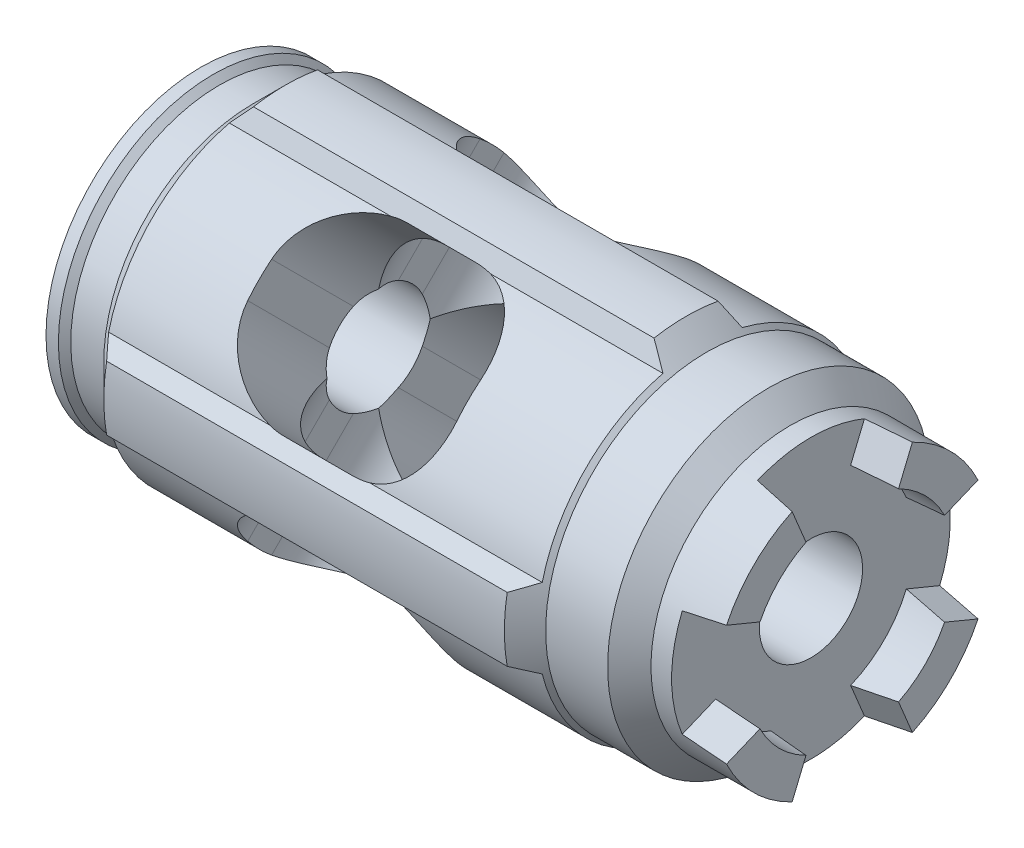
SolidWorks part; units mm, degrees
ref_plane "Front Plane" through (0, 0, 0) normal (0, 0, 1) x (1, 0, 0)
ref_plane "Top Plane" through (0, 0, 0) normal (0, 1, 0) x (1, 0, 0)
ref_plane "Right Plane" through (0, 0, 0) normal (1, 0, 0) x (0, 0, -1)
sketch "Sketch1" plane through (0, 0, 0) normal (0, 0, 1) x (1, 0, 0)
  line L0 (0, 6.35) -> (0, 9.525)
  line L1 (0, 9.525) -> (0.762, 9.525)
  line L2 (0.762, 9.525) -> (1.143, 9.144)
  line L3 (1.143, 9.144) -> (3.175, 9.144)
  line L4 (3.175, 9.144) -> (4.191, 10.16)
  line L5 (4.191, 10.16) -> (30.861, 10.16)
  line L6 (30.861, 10.16) -> (31.115, 9.906)
  line L7 (31.115, 9.906) -> (34.925, 9.906)
  line L8 (34.925, 9.906) -> (36.2585, 8.5725)
  line L9 (36.2585, 8.5725) -> (37.5285, 8.5725)
  line L10 (37.5285, 8.5725) -> (37.5285, 0)
  line L11 (37.5285, 0) -> (6.35, 0)
  line L12 (37.5285, 3.175) -> (5.4993, 3.175) construction
  line L13 (0, 6.35) -> (0, 0)
  line L14 (0, 0) -> (6.35, 0)
  line L15 (5.4993, 3.175) -> (0, 3.175) construction
  arc A0 (0, 6.35) -> (6.35, 0) centre (0, 0) cw construction
  dimension "D13" = 6.35
  dimension "D2" = 0.762
  dimension "D3" = 0.381
  dimension "D4" = 2.032
  dimension "D5" = 135
  dimension "D6" = 10.16
  dimension "D7" = 26.67
  dimension "D8" = 0.254
  dimension "D9" = 3.81
  dimension "D10" = 8.5725
  dimension "D11" = 1.27
  dimension "D12" = 1.016
  dimension "D14" = 3.175
revolve "Revolve1" add sketch "Sketch1" angle 360 about L11
sketch "Sketch2" plane through (0, 0, 0) normal (0, 0, 1) x (1, 0, 0)
  line L0 (30.861, 10.16) -> (4.191, 10.16) construction
  line L1 (30.861, 10.16) -> (4.191, 10.16)
  line L2 (4.191, 10.16) -> (5.207, 11.176)
  line L3 (5.207, 11.176) -> (29.845, 11.176)
  line L4 (29.845, 11.176) -> (30.861, 10.16)
  line L5 (4.191, 10.16) -> (3.175, 9.144) construction
  dimension "D1" = 1.016
revolve "Revolve2" add sketch "Sketch2" angle 20 mid plane about L11
chamfer "Chamfer1" distance 0.762 angle 55 2 edges at (17.526, 10.0056, -1.7643) (17.526, 10.0056, 1.7643)
pattern_circular "CirPattern1" count 4 over 360 about axis through (0, 0, 0) along (1, 0, 0) of "Chamfer1", "Revolve2"
ref_plane "Plane1" through (0, 0, 0) normal (0, 0.7071, 0.7071) x (-1, 0, 0)
sketch "Sketch3" plane through (0, 0, 0) normal (0, 0.7071, 0.7071) x (-1, 0, 0)
  line L0 (-4.191, 5.2503) -> (-4.191, -5.2503) construction
  line L1 (-15.0812, 5.3578) -> (-19.304, 5.3578)
  line L2 (-10.7632, 1.0398) -> (-10.7632, -1.0398)
  line L3 (-15.0812, -5.3578) -> (-19.304, -5.3578)
  line L4 (-23.622, 1.0398) -> (-23.622, -1.0398)
  arc A0 (-10.7632, -1.0398) -> (-15.0812, -5.3578) centre (-15.0812, -1.0398) cw
  arc A1 (-19.304, 5.3578) -> (-23.622, 1.0398) centre (-19.304, 1.0398) ccw
  arc A2 (-19.304, -5.3578) -> (-23.622, -1.0398) centre (-19.304, -1.0398) cw
  arc A3 (-15.0812, 5.3578) -> (-10.7632, 1.0398) centre (-15.0812, 1.0398) cw
  point P4 (-10.7632, 0)
  dimension "D1" = 4.318
  dimension "D2" = 6.5722
  dimension "D3" = 12.8587
  dimension "D4" = 10.7156
extrude "Cut-Extrude1" cut sketch "Sketch3" along normal through all
sketch "Sketch4" plane through (37.5285, 0, 0) normal (1, 0, 0) x (0, 0, -1)
  line L0 (0, 6.35) -> (0, 9.525) construction
  line L1 (7.92, 3.2806) -> (5.8666, 2.43)
  line L2 (2.43, 5.8666) -> (3.2806, 7.92)
  circle A0 centre (0, 0) radius 8.5725 construction
  circle A1 centre (0, 0) radius 8.5725
  circle A2 centre (0, 0) radius 6.35
  circle M4 centre (0, 0) radius 8.5725
  dimension "D1" = 12.7
  dimension "D2" = 45
  dimension "D3" = 22.5
extrude "Boss-Extrude1" add sketch "Sketch4" along normal blind 2.54 contours A2 L1 L2 M4
chamfer "Chamfer2" distance 0.4572 angle 80 2 edges at (40.0685, 6.8933, -2.8553) (40.0685, 2.8553, -6.8933)
pattern_circular "CirPattern2" count 4 over 360 about axis through (0, 0, 0) along (1, 0, 0) of "Cut-Extrude1", "Chamfer2", "Boss-Extrude1"
hole_wizard "1/2 (0.5) Diameter Hole1" positions "Sketch5" profile "Sketch7" hole size "1/2" standard "ANSI Inch"
sketch "Sketch5" plane through (0, 0, 0) normal (-1, 0, 0) x (0, 0, 1)
  point P0 (0, 0)
sketch "Sketch7" plane through (0, 0, 0) normal (0, 1, 0) x (0, 0, 1)
  line L0 (0, 0) -> (0, 7.1175)
  line L1 (0, 7.1175) -> (6.35, 3.302)
  line L2 (6.35, 3.302) -> (6.35, 0)
  line L5 (6.35, 0) -> (0, 0)
  line L10 (0, 7.1175) -> (-6.35, 3.302) construction
  line L11 (0, -6.35) -> (0, 107.95) construction
  dimension "Hole Dia." = 12.7
  dimension "Hole Depth" = 3.302
  dimension "Drill Angle" = 118
hole_wizard "1/4 (0.25) Diameter Hole1" positions "Sketch8" profile "Sketch9" hole size "1/4" standard "ANSI Inch"
sketch "Sketch8" plane through (0, 0, 0) normal (-1, 0, 0) x (0, 0, 1)
  point P0 (0, 0)
sketch "Sketch9" plane through (0, 0, 0) normal (0, 1, 0) x (0, 0, 1)
  line L0 (0, 0) -> (0, 20.9577)
  line L1 (0, 20.9577) -> (3.175, 19.05)
  line L2 (3.175, 19.05) -> (3.175, 0)
  line L5 (3.175, 0) -> (0, 0)
  line L10 (0, 20.9577) -> (-3.175, 19.05) construction
  line L11 (0, -6.35) -> (0, 107.95) construction
  dimension "Hole Dia." = 6.35
  dimension "Hole Depth" = 19.05
  dimension "Drill Angle" = 118
hole_wizard "1/4 (0.25) Diameter Hole2" positions "Sketch10" profile "Sketch11" hole size "1/4" standard "ANSI Inch" end condition through all
sketch "Sketch10" plane through (0, 0, 0) normal (-1, 0, 0) x (0, 0, 1)
  point P0 (0, 0)
sketch "Sketch11" plane through (0, 0, 0) normal (0, 1, 0) x (0, 0, 1)
  line L0 (0, 0) -> (0, 40.0685)
  line L1 (0, 40.0685) -> (3.175, 40.0685)
  line L2 (3.175, 40.0685) -> (3.175, 0)
  line L5 (3.175, 0) -> (0, 0)
  line L11 (0, -6.35) -> (0, 107.95) construction
  dimension "Thru Hole Dia." = 6.35
  dimension "Thru Hole Depth" = 40.0685
